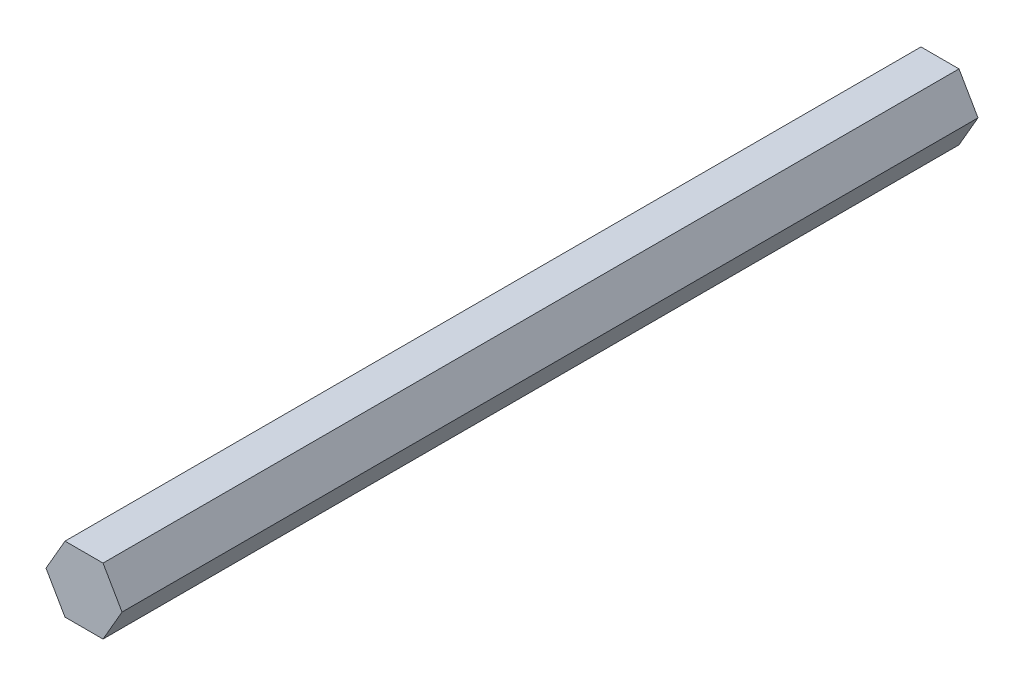
SolidWorks part; units mm, degrees
ref_plane "Front Plane" through (0, 0, 0) normal (0, 0, 1) x (1, 0, 0)
ref_plane "Top Plane" through (0, 0, 0) normal (0, 1, 0) x (1, 0, 0)
ref_plane "Right Plane" through (0, 0, 0) normal (1, 0, 0) x (0, 0, -1)
sketch "Sketch1" plane through (0, 0, 0) normal (0, 0, 1) x (1, 0, 0)
  line L1 (3.6635, -6.3515) -> (7.3323, -0.003)
  line L2 (7.3323, -0.003) -> (3.6688, 6.3485)
  line L3 (3.6688, 6.3485) -> (-3.6635, 6.3515)
  line L4 (-3.6635, 6.3515) -> (-7.3323, 0.003)
  line L5 (-7.3323, 0.003) -> (-3.6688, -6.3485)
  line L6 (-3.6688, -6.3485) -> (3.6635, -6.3515)
  circle A0 centre (0, 0) radius 6.35 construction
  dimension "D1" = 12.7
extrude "Boss-Extrude1" add sketch "Sketch1" along normal blind 165.1
